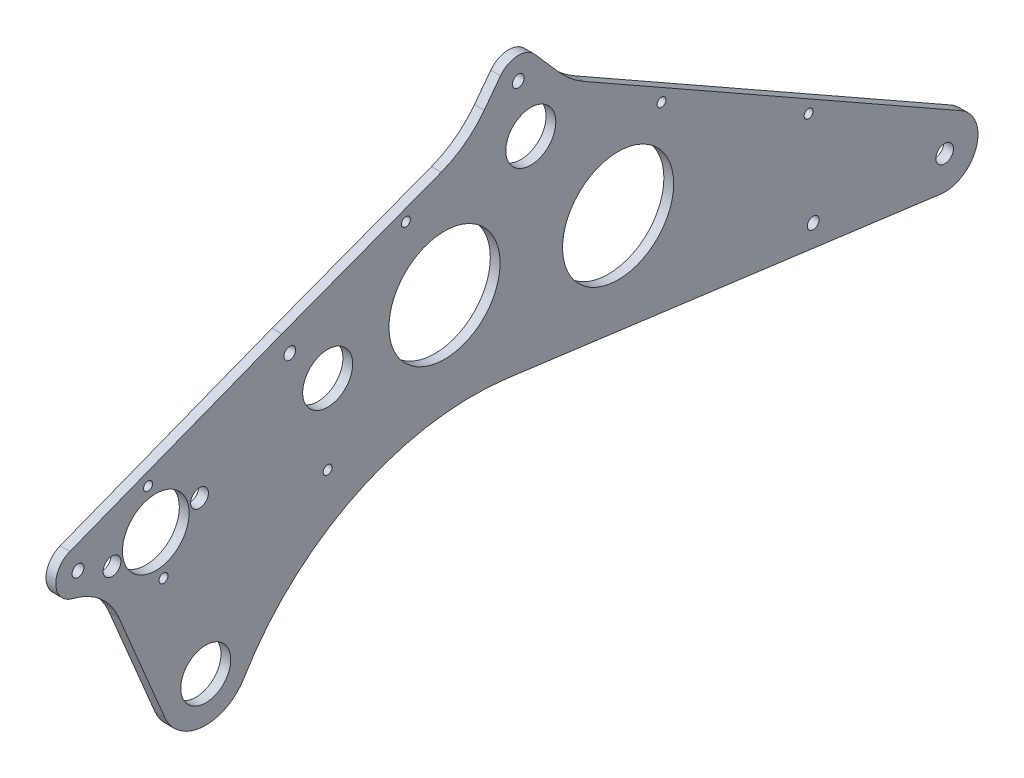
SolidWorks part; units mm, degrees
material "Acrylic (Medium-high impact)"
ref_plane "Front" through (0, 0, 0) normal (0, 0, 1) x (1, 0, 0)
ref_plane "Top" through (0, 0, 0) normal (0, 1, 0) x (1, 0, 0)
ref_plane "Right" through (0, 0, 0) normal (1, 0, 0) x (0, 0, -1)
sketch "Sketch1" plane through (0, 0, 0) normal (1, 0, 0) x (0, 0, -1)
  line L0 (-128.5875, -88.9) -> (-128.5875, -215.9)
  line L1 (-128.5875, -215.9) -> (-179.3875, -215.9)
  line L2 (-211.1375, -184.15) -> (-211.1375, -120.65)
  line L3 (-179.3875, -88.9) -> (-128.5875, -88.9)
  line L4 (-30.1658, -279.4) -> (-969.8164, -279.4) construction
  line L5 (-433.3875, -184.15) -> (-433.3875, -120.65) construction
  line L6 (-120.65, -76.2) -> (-95.25, -76.2)
  line L7 (-120.65, -76.2) -> (-120.65, -101.6)
  line L8 (-120.65, -101.6) -> (-95.25, -101.6)
  line L9 (-95.25, -76.2) -> (-95.25, -101.6)
  line L10 (-179.3875, 133.35) -> (-128.5875, 133.35) construction
  line L11 (-422.2889, -46.3876) -> (-179.3875, -120.65) construction
  line L12 (-352.6151, 65.1138) -> (-179.3875, -120.65) construction
  line L13 (-236.5251, 126.84) -> (-179.3875, -120.65) construction
  line L14 (-352.6151, 65.1138) -> (-329.3692, 41.8679) construction
  line L17 (-128.5875, -88.9) -> (-128.5875, 537.2462) construction
  line L19 (-534.9875, 265.7496) -> (-534.9875, -127.8462) construction
  line L20 (-441.2356, -52.7925) -> (-469.7967, 31.6951)
  line L21 (-456.153, 57.3841) -> (-357.9181, 84.398)
  line L22 (-336.8745, 52.7755) -> (-358.8621, 24.7249)
  line L23 (-346.2875, 15.0359) -> (-252.4687, 138.9148)
  line L24 (-222.8851, 112.2129) -> (-408.6489, -61.0147)
  circle A0 centre (0, 0) radius 5.0419
  circle A1 centre (-422.2889, -46.3876) radius 11.557
  circle A2 centre (-352.6151, 65.1138) radius 11.557
  circle A3 centre (-236.5251, 126.84) radius 11.557
  arc A4 (-179.3875, -215.9) -> (-211.1375, -184.15) centre (-179.3875, -184.15) cw
  arc A5 (-211.1375, -120.65) -> (-179.3875, -88.9) centre (-179.3875, -120.65) cw
  circle A6 centre (-286.3288, -36.0608) radius 120.65
  arc A7 (-433.3875, -120.65) -> (-179.3875, 133.35) centre (-179.3875, -120.65) cw construction
  circle A12 centre (-450.85, 38.1) radius 31.75
  arc A19 (-408.6489, -61.0147) -> (-441.2356, -52.7925) centre (-422.2889, -46.3876) cw
  arc A20 (-469.7967, 31.6951) -> (-456.153, 57.3841) centre (-450.85, 38.1) cw
  arc A21 (-357.9181, 84.398) -> (-336.8745, 52.7755) centre (-352.6151, 65.1138) cw
  arc A22 (-358.8621, 24.7249) -> (-346.2875, 15.0359) centre (-352.6151, 19.8281) ccw
  arc A23 (-252.4687, 138.9148) -> (-222.8851, 112.2129) centre (-236.5251, 126.84) cw
  point P23 (0, 0)
  point P24 (0, 0)
  point P33 (-319.4096, -143.737)
  point P35 (-514.8091, -147.9459)
  point P36 (-329.3692, -161.1737)
  point P37 (-350.2773, 18.1167)
  point P38 (0, 0)
  point P40 (-320.9115, -160.7399)
  point P41 (-128.5875, 537.2462)
  point P42 (-329.3692, -156.7882)
  point P43 (-385.3502, -152.4)
  point P44 (-286.3288, -36.0608)
  circle B0 centre (-236.5251, 126.84) radius 20
  circle B1 centre (-352.6151, 65.1138) radius 20
  circle B2 centre (-422.2889, -46.3876) radius 20
  circle B3 centre (-450.85, 38.1) radius 20
  circle B4 centre (-352.6151, 19.8281) radius 7.9375
  dimension "D1" = 10.0838
  dimension "D2" = 23.114
  dimension "D4" = 31.75
  dimension "D10" = 241.3
  dimension "D19" = 63.5
  dimension "D22" = 322.2625
  dimension "D26" = 46.3876
  dimension "D27" = 422.2889
  dimension "D23" = 127
  dimension "D3" = 127
  dimension "D5" = 82.55
  dimension "D6" = 190.5
  dimension "D7" = 25.4
  dimension "D8" = 7.9375
  dimension "D9" = 203.2
  dimension "D12" = 120.65
  dimension "D13" = 76.2
  dimension "D14" = 30
  dimension "D15" = 30
  dimension "D16" = 17
  dimension "D24" = 406.4
  dimension "D25" = 45
  dimension "D11" = 222.25
sketch_block_instance "Block1-1"
sketch_block "Block1" parameters "D1"=40
sketch_block_instance "Block2-1"
sketch_block "Block2"
sketch_block_instance "Block3-1"
sketch_block "Block3"
sketch_block_instance "Block4-1"
sketch_block "Block4" parameters "D1"=40
sketch_block_instance "Block5-1"
sketch_block "Block5" parameters "D1"=15.875
other "Belt2"
sketch "Sketch3" plane through (0, 0, 0) normal (1, 0, 0) x (0, 0, -1)
  line L0 (-422.2889, -46.3876) -> (0, 0) construction
  line L1 (0, 0) -> (-75.1219, 3.2799) construction
  line L2 (0, 0) -> (-83.016, 416.639) construction
  line L3 (0, 0) -> (-3.2799, 75.1219) construction
  line L4 (-75.1219, 3.2799) -> (-73.8703, -8.1145) construction
  line L5 (-3.2799, 75.1219) -> (-14.5218, 72.882) construction
  line L6 (-3.2799, 75.1219) -> (-75.1219, 3.2799)
  line L7 (173.721, 252.1228) -> (-3.2799, 75.1219)
  line L8 (0, 0) -> (105.7428, 246.6799) construction
  line L9 (0, 0) -> (-236.5251, 126.84) construction
  line L10 (-236.5251, 126.84) -> (-219.938, -24.1598) construction
  line L11 (105.7428, 246.6799) -> (-43.2367, 216.9955) construction
  line L12 (128.0302, 224.3925) -> (145.9907, 206.432)
  circle A0 centre (-83.016, 416.639) radius 25.4
  circle A1 centre (105.7428, 246.6799) radius 20
  circle A2 centre (-236.5251, 126.84) radius 20 construction
  point P22 (137.0104, 215.4123)
  dimension "D1" = 50.8
  dimension "D2" = 85
  dimension "D3" = 101.6
  dimension "D4" = 250.317
  dimension "D5" = 45
  dimension "D6" = 25.4
sketch "Sketch2" plane through (0, 0, 0) normal (1, 0, 0) x (0, 0, -1)
  line L0 (-445.711, -56.2145) -> (-472.0658, 6.6014)
  line L1 (-499.9046, 53.0838) -> (-378.8732, 100.1702)
  line L2 (-422.2889, -46.3876) -> (-422.2889, 0) construction
  line L3 (-378.7603, 100.2135) -> (-287.6887, 134.6492)
  line L4 (9.3977, 16.5706) -> (-205.9604, 138.7063)
  line L6 (-249.5854, 13.7262) -> (-2.4927, -18.8862)
  line L7 (-374.2685, 88.3343) -> (-352.6151, 65.1138) construction
  line L8 (-263.1162, 153.0695) -> (-253.8099, 165.4193)
  line L9 (-234.1216, 166.1531) -> (-220.2253, 150.3178)
  line L10 (-236.5251, 126.84) -> (-179.3875, -120.65) construction
  line L11 (-243.6673, 157.7762) -> (-236.5251, 126.84) construction
  line L12 (-236.5251, 126.84) -> (-219.938, -24.1598) construction
  line L13 (-475.8641, 33.6893) -> (-425.8359, 42.5107) construction
  line L14 (-455.2607, 63.1141) -> (-446.4393, 13.0859) construction
  line L15 (-450.85, 38.1) -> (-450.85, 54.7353) construction
  circle A0 centre (-236.5251, 126.84) radius 14.2875
  circle A1 centre (-352.6151, 65.1138) radius 14.2875
  circle A2 centre (-422.2889, -46.3876) radius 14.2875
  circle A3 centre (-450.85, 38.1) radius 19.05
  circle A4 centre (-352.6151, 19.8281) radius 2.5527
  circle A9 centre (0, 0) radius 5.0419 construction
  circle A10 centre (0, 0) radius 5.0419
  arc A13 (-445.711, -56.2145) -> (-400.4658, -59.3841) centre (-422.2889, -46.3876) ccw
  arc A16 (-2.4927, -18.8862) -> (9.3977, 16.5706) centre (0, 0) ccw
  arc A18 (-249.5854, 13.7262) -> (-400.4658, -59.3841) centre (-269.5269, -137.3635) ccw
  circle A19 centre (-75.1219, 3.2799) radius 3.3782
  circle A20 centre (-374.2685, 88.3343) radius 3.3782
  arc A21 (-378.8732, 100.1702) -> (-378.7603, 100.2135) centre (-374.2685, 88.3343) cw
  circle A22 centre (-243.6673, 157.7762) radius 3.3782
  arc A23 (-253.8099, 165.4193) -> (-234.1216, 166.1531) centre (-243.6673, 157.7762) cw
  circle A24 centre (-236.5251, 126.84) radius 25.4 construction
  arc A25 (-220.2253, 150.3178) -> (-205.9604, 138.7063) centre (-178.7172, 186.7434) ccw
  arc A26 (-263.1162, 153.0695) -> (-287.6887, 134.6492) centre (-307.2205, 186.3044) cw
  circle A27 centre (-425.8359, 42.5107) radius 5.08
  circle A28 centre (-455.2607, 63.1141) radius 2.5527
  circle A29 centre (-475.8641, 33.6893) radius 5.08
  circle A30 centre (-446.4393, 13.0859) radius 2.5527
  circle A31 centre (-450.85, 38.1) radius 25.4 construction
  circle A32 centre (-495.3, 41.2479) radius 3.3782
  arc A34 (-499.9046, 53.0838) -> (-498.2747, 28.9012) centre (-495.3, 41.2479) ccw
  arc A35 (-498.2747, 28.9012) -> (-472.0658, 6.6014) centre (-507.1989, -8.1389) cw
  circle A37 centre (-450.85, 38.1) radius 31.75 construction
  dimension "D1" = 28.575
  dimension "D2" = 38.1
  dimension "D3" = 5.1054
  dimension "D4" = 50.8
  dimension "D5" = 12.7
  dimension "D6" = 6.7564
  dimension "D7" = 19.05
  dimension "D8" = 152.4
  dimension "D10" = 6.7564
  dimension "D11" = 12.7
  dimension "D12" = 31.75
  dimension "D13" = 12.7
  dimension "D14" = 31.75
  dimension "D17" = 55.2245
  dimension "D18" = 5.1054
  dimension "D19" = 10.16
  dimension "D20" = 50.8
  dimension "D21" = 25.4
  dimension "D22" = 38.1
  dimension "D23" = 44.45
  dimension "D9" = 25.4
  dimension "D15" = 50
  dimension "D16" = 35
  dimension "D24" = 10
extrude "Boss-Extrude1" add sketch "Sketch2" along normal blind 5.588
sketch "Sketch4" plane through (5.588, 0, 0) normal (1, 0, 0) x (0, 0, -1)
  line L0 (-352.6151, 65.1138) -> (-236.5251, 126.84) construction
  line L1 (-306.5028, 127.5353) -> (-285.8289, 72.8594) construction
  line L2 (-287.6887, 134.6492) -> (-378.7603, 100.2135) construction
  line L3 (-285.8289, 72.8594) -> (-281.3096, 14.5804) construction
  line L4 (-281.3096, 14.5804) -> (-269.5269, -137.3635) construction
  line L5 (-158.6748, 111.8894) -> (-186.6352, 62.5877) construction
  line L6 (9.3977, 16.5706) -> (-205.9604, 138.7063) construction
  line L7 (-186.6352, 62.5877) -> (-194.0516, 6.3966) construction
  line L8 (-249.5854, 13.7262) -> (-2.4927, -18.8862) construction
  line L9 (-374.2685, 88.3343) -> (-243.6673, 157.7762) construction
  line L10 (-310.1416, 126.1594) -> (-308.9679, 123.0553) construction
  line L11 (-245.8065, 154.0041) -> (-161.7827, 106.3518) construction
  line L12 (-161.7827, 106.3518) -> (-77.7588, 58.6994) construction
  line L13 (-77.7588, 58.6994) -> (6.2651, 11.0471) construction
  line L14 (-245.8065, 154.0041) -> (-243.6673, 157.7762) construction
  line L15 (0, 0) -> (6.2651, 11.0471) construction
  circle A0 centre (-285.8289, 72.8594) radius 31.75
  circle A1 centre (-186.6352, 62.5877) radius 31.75
  arc A2 (-249.5854, 13.7262) -> (-400.4658, -59.3841) centre (-269.5269, -137.3635) ccw construction
  circle A3 centre (-307.8958, 120.2198) radius 2.54
  circle A5 centre (-161.7827, 106.3518) radius 2.54
  circle A6 centre (-77.7588, 58.6994) radius 2.54
  point P2 (-294.5701, 95.9769)
  dimension "D1" = 63.5
  dimension "D2" = 63.5
  dimension "D3" = 196.85
  dimension "D4" = 5.08
  dimension "D5" = 6.35
  dimension "D6" = 6.35
extrude "Cut-Extrude1" cut sketch "Sketch4" against normal through all
